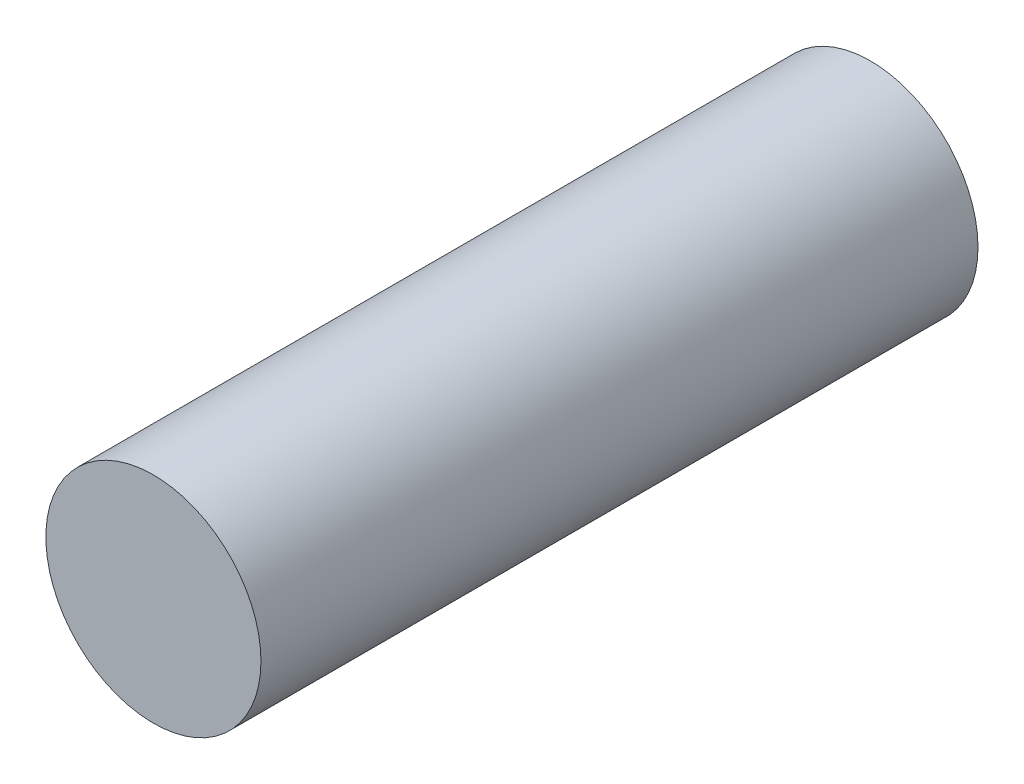
SolidWorks part; units mm, degrees
ref_plane "Front Plane" through (0, 0, 0) normal (1, 0, 0) x (0, 1, 0)
ref_plane "Top Plane" through (0, 0, 0) normal (0, 0, 1) x (0, 1, 0)
ref_plane "Right Plane" through (0, 0, 0) normal (0, 1, 0) x (-1, 0, 0)
sketch "Sketch2" plane through (0, 0, 0) normal (0, 0, 1) x (0, 1, 0)
  circle A0 centre (0, 0) radius 10.5
  dimension "D1" = 21
extrude "Boss-Extrude1" add sketch "Sketch2" along normal blind 35 and the other way blind 35
